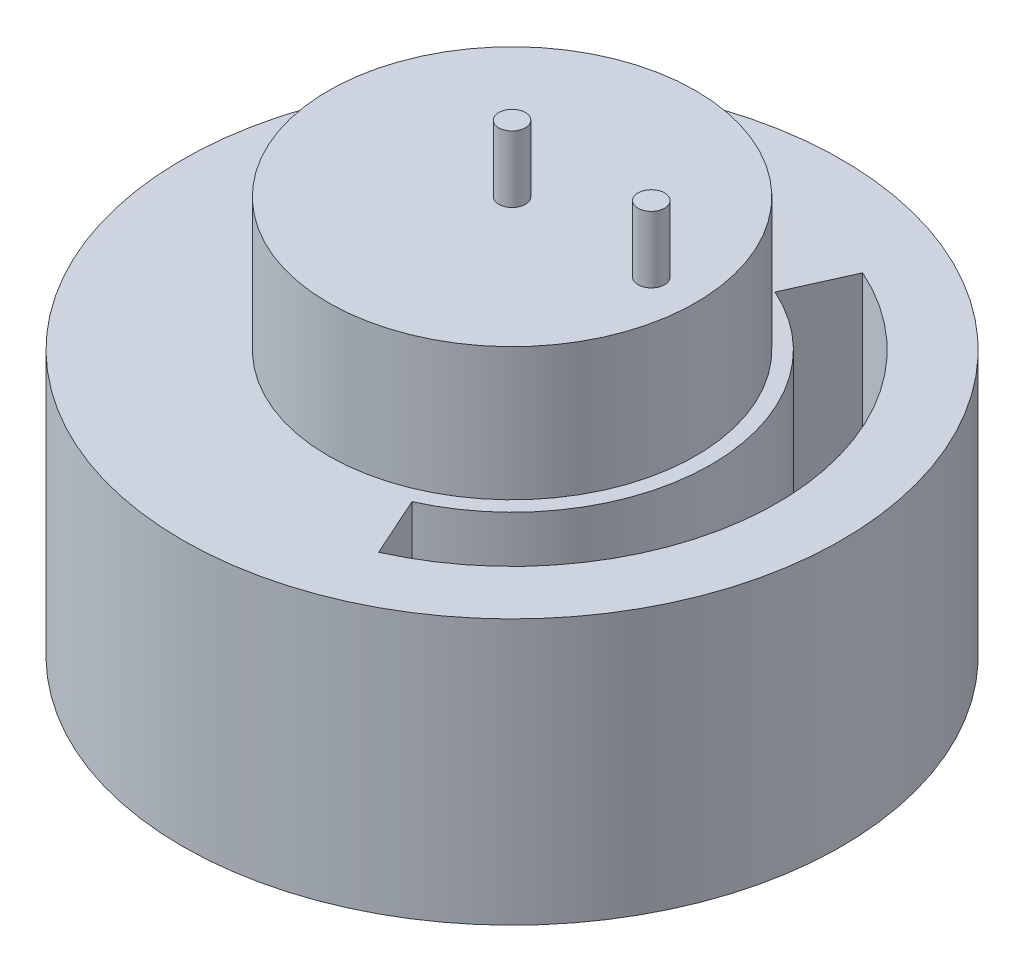
SolidWorks part; units mm, degrees
ref_plane "Plano frontal" through (0, 0, 0) normal (0, 0, 1) x (1, 0, 0)
ref_plane "Plano superior" through (0, 0, 0) normal (0, 1, 0) x (1, 0, 0)
ref_plane "Plano direito" through (0, 0, 0) normal (1, 0, 0) x (0, 0, -1)
sketch "Esboço1" plane through (0, 0, 0) normal (0, 1, 0) x (1, 0, 0)
  line L0 (0, 0) -> (-10, 0) construction
  line L1 (0, 0) -> (10, 0) construction
  line L2 (-10, 0) -> (-10, -17.3205) construction
  line L3 (10, 0) -> (10, -17.3205) construction
  line L4 (10, -27.2235) -> (-10, -27.2235) construction
  line L9 (-10, -22.9129) -> (-10, -27.2235) construction
  line L11 (10, -22.9129) -> (10, -27.2235) construction
  arc A1 (12.425, -21.5207) -> (-12.425, -21.5207) centre (0, 0) ccw
  circle A3 centre (0, 0) radius 24.85
extrude "Ressalto-extrusão2" add sketch "Esboço1" along normal blind 20 contours A1 A3 region at (0, 0, 0)
ref_plane "Plano1" through (0, 20, 0) normal (0, 1, 0) x (1, 0, 0)
sketch "Esboço3" plane through (0, 20, 0) normal (0, 1, 0) x (1, 0, 0)
  circle A0 centre (0, 0) radius 13.85
extrude "Boss-Extrude1" add sketch "Esboço3" along normal blind 10
sketch "Sketch1" plane through (0, 20, 0) normal (0, 1, 0) x (1, 0, 0)
  circle A0 centre (0, 0) radius 20
  circle A1 centre (0, 0) radius 25
ref_plane "Plane1" through (0, 30, 0) normal (0, 1, 0) x (1, 0, 0)
sketch "Sketch2" plane through (0, 30, 0) normal (0, 1, 0) x (1, 0, 0)
  line L0 (1, 0) -> (10.5, 0) construction
  circle A0 centre (0, 0) radius 1
  circle A1 centre (10.5, 0) radius 1
extrude "Boss-Extrude2" add sketch "Sketch2" along normal blind 5
ref_plane "Plane2" through (0, 20, 0) normal (0, 1, 0) x (1, 0, 0)
sketch "Sketch3" plane through (0, 20, 0) normal (0, 1, 0) x (1, 0, 0)
  line L0 (0, 0) -> (15, 0) construction
  line L1 (0, 0) -> (8.1857, -18.2481) construction
  line L2 (0, 0) -> (8.1857, 18.2481) construction
  line L3 (8.1857, -18.2481) -> (6.1393, -13.6861)
  line L4 (8.1857, 18.2481) -> (6.1393, 13.6861)
  arc A0 (6.1393, -13.6861) -> (6.1393, 13.6861) centre (0, 0) ccw
  arc A1 (8.1857, -18.2481) -> (8.1857, 18.2481) centre (0, 0) ccw
  dimension "D1" = 65.84
extrude "Cut-Extrude2" cut sketch "Sketch3" against normal up to surface (20 mm away) up to face at (0, 0, 24.85)
